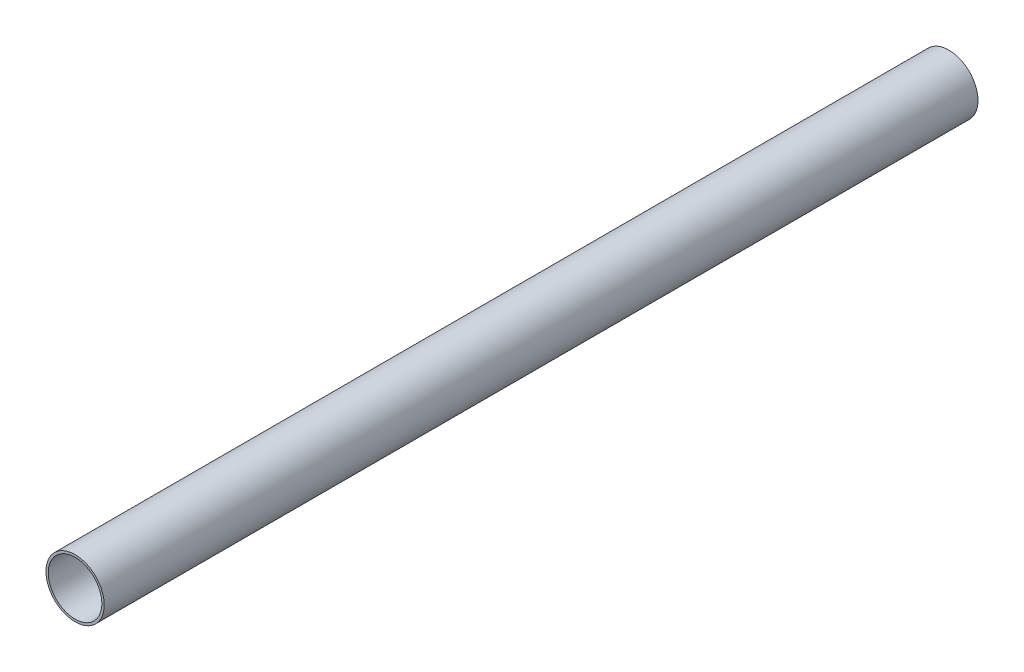
SolidWorks part; units mm, degrees
ref_plane "Спереди" through (0, 0, 0) normal (0, 0, 1) x (1, 0, 0)
ref_plane "Сверху" through (0, 0, 0) normal (0, 1, 0) x (1, 0, 0)
ref_plane "Справа" through (0, 0, 0) normal (1, 0, 0) x (0, 0, -1)
other "Configuration Table"
sketch "Эскиз1" plane through (0, 0, 0) normal (0, 0, 1) x (1, 0, 0)
  circle A0 centre (0, 0) radius 50
  circle A1 centre (0, 0) radius 46
  dimension "D1" = 100
  dimension "D2" = 4
extrude "Бобышка-Вытянуть1" add sketch "Эскиз1" along normal blind 1500
ref_axis "Ось1" through (0, 0, 1500) along (0, 0, -1)
